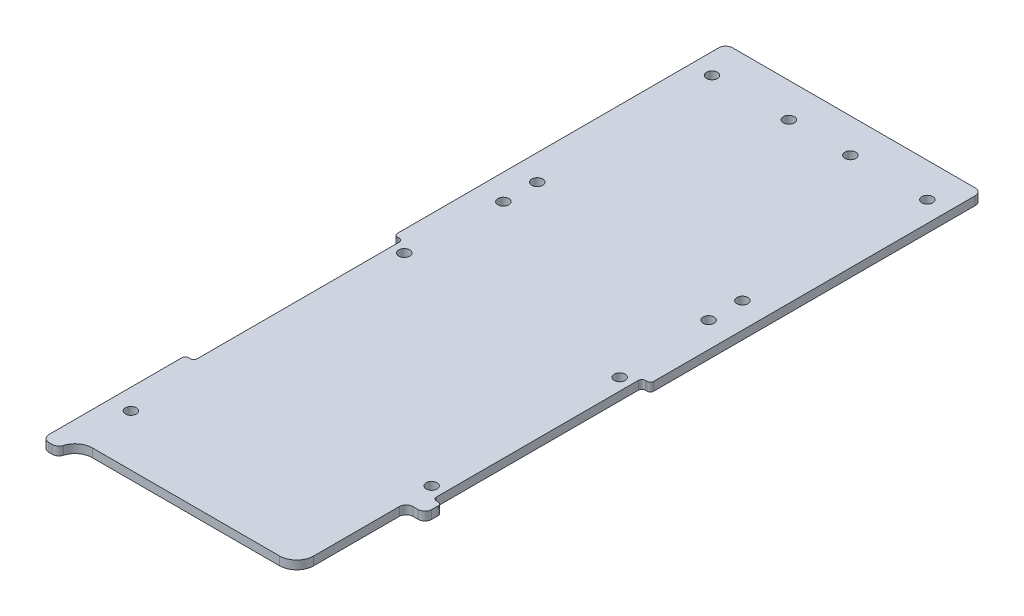
SolidWorks part; units mm, degrees
ref_plane "Front Plane" through (0, 0, 0) normal (0, 0, 1) x (1, 0, 0)
ref_plane "Top Plane" through (0, 0, 0) normal (0, 1, 0) x (1, 0, 0)
ref_plane "Right Plane" through (0, 0, 0) normal (1, 0, 0) x (0, 0, -1)
sketch "Sketch1" plane through (0, 0, 0) normal (0, 1, 0) x (1, 0, 0)
  line L0 (-39.9997, 0) -> (-39.9997, 114.3) construction
  line L1 (-47.625, 127) -> (47.625, 127)
  line L2 (-47.625, 127) -> (-47.625, -127)
  line L3 (-47.625, -127) -> (47.625, -127)
  line L4 (47.625, 127) -> (47.625, -127)
  line L5 (-47.625, 127) -> (47.625, -127) construction
  line L6 (-47.625, -127) -> (47.625, 127) construction
  line L7 (0, 0) -> (0, 127) construction
  line L8 (-39.9997, 0) -> (-39.9997, -101.6) construction
  line L9 (-39.9997, 0) -> (0, 0) construction
  line L10 (-41.275, -127) -> (-41.275, -120.65)
  line L11 (-41.275, -120.65) -> (41.275, -120.65)
  line L12 (41.275, -120.65) -> (41.275, -127)
  line L13 (-39.9997, 114.3) -> (-11.4247, 114.3) construction
  line L14 (39.9997, 114.3) -> (11.4247, 114.3) construction
  circle A0 centre (-39.9997, 114.3) radius 2.032
  circle A1 centre (-39.9997, 0) radius 2.032
  circle A2 centre (-39.9997, -101.6) radius 2.032
  circle A3 centre (39.9997, -101.6) radius 2.032
  circle A4 centre (39.9997, 0) radius 2.032
  circle A5 centre (39.9997, 114.3) radius 2.032
  circle A6 centre (-11.4247, 114.3) radius 2.032
  circle A7 centre (11.4247, 114.3) radius 2.032
  circle A8 centre (-39.9997, -69.85) radius 2.032
  circle A9 centre (39.9997, -69.85) radius 2.032
  point P0 (0, 0)
  dimension "D4" = 4.064
  dimension "D10" = 28.575
  dimension "D1" = 95.25
  dimension "D2" = 254
  dimension "D3" = 7.6253
  dimension "D5" = 12.7
  dimension "D6" = 25.4
  dimension "D7" = 6.35
  dimension "D8" = 6.35
  dimension "D9" = 6.35
  dimension "D11" = 69.85
extrude "Boss-Extrude1" add sketch "Sketch1" along normal blind 3.175 contours L4 L1 L2 L3 A4 A0 A1 A2 A3 A5 | A8 | A3 region at (0, 0, -2.6944) region at (39.9997, 0, 101.6) region at (-39.9997, 0, 69.85)
fillet "Fillet1" radius 2.54 4 edges at (-47.625, 1.5875, -127) (47.625, 1.5875, -127) (47.625, 1.5875, 127) (-47.625, 1.5875, 127)
fillet "Fillet2" radius 2.54 2 edges at (41.275, 1.5875, 127) (-41.275, 1.5875, 127)
fillet "Fillet3" radius 6.35 2 edges at (41.275, 1.5875, 120.65) (-41.275, 1.5875, 120.65)
sketch "Sketch2" plane through (0, 0, 0) normal (0, -1, 0) x (1, 0, 0)
  line L0 (41.9117, 131.8831) -> (41.9117, 109.8659) construction
  line L1 (41.9117, 109.8659) -> (41.9117, 106.3879) construction
  line L2 (41.9117, 83.271) -> (41.9117, 82.5325) construction
  line L3 (41.9117, 82.5325) -> (41.9117, 81.2514) construction
  line L4 (41.9117, 83.271) -> (41.9117, 106.3879) construction
  line L5 (41.9117, 131.8831) -> (41.9117, 109.8659)
  line L6 (41.9117, 109.8659) -> (41.9117, 106.3879)
  line L7 (41.9117, 83.271) -> (41.9117, 82.5325)
  line L8 (41.9117, 82.5325) -> (41.9117, 81.2514)
  line L9 (41.9117, 83.271) -> (41.9117, 106.3879)
  line L10 (41.9117, 81.2514) -> (47.625, 81.2514)
  line L11 (47.625, -124.46) -> (47.625, 124.46) construction
  line L12 (41.9117, 131.8831) -> (47.625, 131.8831)
  line L13 (47.625, 131.8831) -> (47.625, 81.2514)
  line L14 (40.6417, 79.9814) -> (48.895, 79.9814)
  line L15 (48.895, 133.1531) -> (48.895, 79.9814)
  line L16 (40.6417, 133.1531) -> (48.895, 133.1531)
  line L17 (40.6417, 133.1531) -> (40.6417, 109.8659)
  line L18 (40.6417, 109.8659) -> (40.6417, 106.3879)
  line L19 (40.6417, 83.271) -> (40.6417, 106.3879)
  line L20 (40.6417, 83.271) -> (40.6417, 82.5325)
  line L21 (40.6417, 82.5325) -> (40.6417, 79.9814)
  arc M7 (43.815, 127) -> (41.3809, 125.1857) centre (43.815, 124.46) ccw
  arc M8 (41.3809, 125.1857) -> (35.2956, 120.65) centre (35.2956, 127) cw
  line M18 (47.625, -124.46) -> (47.625, 124.46)
  dimension "D1" = 1.27
extrude "Cut-Extrude1" cut sketch "Sketch2" against normal through all contours L20 L21 L14 L10 L8 L7 L9 L19 M18 | L19 L9 L6 L5 L17 L18 M7 M8 | L13 L10 L8 L7 L9 L6 L5 L12 region at (41.6767, 0, 99.9811)
fillet "Fillet4" radius 6.35 1 edges at (40.6417, 1.5875, 123.5734)
fillet "Fillet5" radius 2.54 2 edges at (47.625, 1.5875, 79.9814) (40.6417, 1.5875, 79.9814)
sketch "Sketch3" plane through (0, 0, 0) normal (0, -1, 0) x (1, 0, 0)
  line L0 (-36.3088, -49.7791) -> (-39.9156, -49.7791) construction
  line L1 (-40.4236, -49.276) -> (-40.4236, -45.7043) construction
  line L2 (-35.8008, -45.7043) -> (-35.8008, -49.276) construction
  line L3 (-39.9156, -45.2013) -> (-36.3088, -45.2013) construction
  line L4 (-36.3088, -37.2027) -> (-39.9156, -37.2027) construction
  line L5 (-35.8008, -33.1279) -> (-35.8008, -36.6996) construction
  line L6 (-40.4236, -36.6996) -> (-40.4236, -33.1279) construction
  line L7 (-39.9156, -32.6249) -> (-36.3088, -32.6249) construction
  line L8 (36.2844, -32.6249) -> (39.8912, -32.6249) construction
  line L9 (40.3992, -33.1279) -> (40.3992, -36.6996) construction
  line L10 (39.8912, -37.2027) -> (36.2844, -37.2027) construction
  line L11 (35.7764, -36.6996) -> (35.7764, -33.1279) construction
  line L12 (36.2844, -45.2013) -> (39.8912, -45.2013) construction
  line L13 (35.7764, -49.276) -> (35.7764, -45.7043) construction
  line L14 (40.3992, -45.7043) -> (40.3992, -49.276) construction
  line L15 (39.8912, -49.7791) -> (36.2844, -49.7791) construction
  line L16 (-36.3088, -49.7791) -> (-39.9156, -49.7791)
  line L17 (-40.4236, -49.276) -> (-40.4236, -45.7043)
  line L18 (-35.8008, -45.7043) -> (-35.8008, -49.276)
  line L19 (-39.9156, -45.2013) -> (-36.3088, -45.2013)
  line L20 (-36.3088, -37.2027) -> (-39.9156, -37.2027)
  line L21 (-35.8008, -33.1279) -> (-35.8008, -36.6996)
  line L22 (-40.4236, -36.6996) -> (-40.4236, -33.1279)
  line L23 (-39.9156, -32.6249) -> (-36.3088, -32.6249)
  line L24 (36.2844, -32.6249) -> (39.8912, -32.6249)
  line L25 (40.3992, -33.1279) -> (40.3992, -36.6996)
  line L26 (39.8912, -37.2027) -> (36.2844, -37.2027)
  line L27 (35.7764, -36.6996) -> (35.7764, -33.1279)
  line L28 (36.2844, -45.2013) -> (39.8912, -45.2013)
  line L29 (35.7764, -49.276) -> (35.7764, -45.7043)
  line L30 (40.3992, -45.7043) -> (40.3992, -49.276)
  line L31 (39.8912, -49.7791) -> (36.2844, -49.7791)
  line L32 (-47.625, -25.836) -> (47.625, -25.836)
  line L33 (-47.625, -124.46) -> (-47.625, 124.46) construction
  line L34 (47.625, -124.46) -> (47.625, 77.4414) construction
  line L35 (0, -25.836) -> (0, -56.0686) construction
  line L38 (134.362, -51.414) -> (184.1378, -51.414)
  line L39 (184.1378, -51.414) -> (184.1378, -43.4909)
  line L40 (184.1378, -43.4909) -> (182.3344, -43.4909)
  line L41 (181.8264, -42.9878) -> (181.8264, -39.4161)
  line L42 (182.3344, -38.9131) -> (184.1378, -38.9131)
  line L43 (184.1378, -38.9131) -> (184.1378, -30.9899)
  line L44 (184.1378, -30.9899) -> (134.362, -30.9899)
  line L45 (134.362, -30.9899) -> (133.3378, -32.0042)
  line L46 (133.3378, -32.0042) -> (132.3136, -30.9899)
  line L47 (132.3136, -30.9899) -> (70.862, -30.9899)
  line L48 (70.862, -30.9899) -> (69.8378, -32.0042)
  line L49 (69.8378, -32.0042) -> (68.8136, -30.9899)
  line L50 (68.8136, -30.9899) -> (7.362, -30.9899)
  line L51 (7.362, -30.9899) -> (6.3378, -32.0042)
  line L52 (6.3378, -32.0042) -> (5.3136, -30.9899)
  line L53 (5.3136, -30.9899) -> (-56.138, -30.9899)
  line L54 (-56.138, -30.9899) -> (-57.1622, -32.0042)
  line L55 (-57.1622, -32.0042) -> (-58.1864, -30.9899)
  line L56 (-58.1864, -30.9899) -> (-119.638, -30.9899)
  line L57 (-119.638, -30.9899) -> (-120.6622, -32.0042)
  line L58 (-120.6622, -32.0042) -> (-121.6864, -30.9899)
  line L59 (-121.6864, -30.9899) -> (-184.1622, -30.9899)
  line L60 (-184.1622, -30.9899) -> (-184.1622, -51.414)
  line L61 (-184.1622, -51.414) -> (-121.6864, -51.414)
  line L62 (-121.6864, -51.414) -> (-120.6622, -50.3998)
  line L63 (-120.6622, -50.3998) -> (-119.638, -51.414)
  line L64 (-119.638, -51.414) -> (-58.1864, -51.414)
  line L65 (-58.1864, -51.414) -> (-57.1622, -50.3998)
  line L66 (-57.1622, -50.3998) -> (-56.138, -51.414)
  line L67 (-56.138, -51.414) -> (5.3136, -51.414)
  line L68 (5.3136, -51.414) -> (6.3378, -50.3998)
  line L69 (6.3378, -50.3998) -> (7.362, -51.414)
  line L70 (7.362, -51.414) -> (68.8136, -51.414)
  line L71 (68.8136, -51.414) -> (69.8378, -50.3998)
  line L72 (69.8378, -50.3998) -> (70.862, -51.414)
  line L73 (70.862, -51.414) -> (132.3136, -51.414)
  line L74 (132.3136, -51.414) -> (133.3378, -50.3998)
  line L75 (133.3378, -50.3998) -> (134.362, -51.414)
  line L76 (134.362, -51.414) -> (184.1378, -51.414)
  line L77 (184.1378, -51.414) -> (184.1378, -43.4909)
  line L78 (184.1378, -43.4909) -> (182.3344, -43.4909)
  line L79 (181.8264, -42.9878) -> (181.8264, -39.4161)
  line L80 (182.3344, -38.9131) -> (184.1378, -38.9131)
  line L81 (184.1378, -38.9131) -> (184.1378, -30.9899)
  line L82 (184.1378, -30.9899) -> (134.362, -30.9899)
  line L83 (134.362, -30.9899) -> (133.3378, -32.0042)
  line L84 (133.3378, -32.0042) -> (132.3136, -30.9899)
  line L85 (132.3136, -30.9899) -> (70.862, -30.9899)
  line L86 (70.862, -30.9899) -> (69.8378, -32.0042)
  line L87 (69.8378, -32.0042) -> (68.8136, -30.9899)
  line L88 (68.8136, -30.9899) -> (7.362, -30.9899)
  line L89 (7.362, -30.9899) -> (6.3378, -32.0042)
  line L90 (6.3378, -32.0042) -> (5.3136, -30.9899)
  line L91 (5.3136, -30.9899) -> (-56.138, -30.9899)
  line L92 (-56.138, -30.9899) -> (-57.1622, -32.0042)
  line L93 (-57.1622, -32.0042) -> (-58.1864, -30.9899)
  line L94 (-58.1864, -30.9899) -> (-119.638, -30.9899)
  line L95 (-119.638, -30.9899) -> (-120.6622, -32.0042)
  line L96 (-120.6622, -32.0042) -> (-121.6864, -30.9899)
  line L97 (-121.6864, -30.9899) -> (-184.1622, -30.9899)
  line L98 (-184.1622, -30.9899) -> (-184.1622, -51.414)
  line L99 (-184.1622, -51.414) -> (-121.6864, -51.414)
  line L100 (-121.6864, -51.414) -> (-120.6622, -50.3998)
  line L101 (-120.6622, -50.3998) -> (-119.638, -51.414)
  line L102 (-119.638, -51.414) -> (-58.1864, -51.414)
  line L103 (-58.1864, -51.414) -> (-57.1622, -50.3998)
  line L104 (-57.1622, -50.3998) -> (-56.138, -51.414)
  line L105 (-56.138, -51.414) -> (5.3136, -51.414)
  line L106 (5.3136, -51.414) -> (6.3378, -50.3998)
  line L107 (6.3378, -50.3998) -> (7.362, -51.414)
  line L108 (7.362, -51.414) -> (68.8136, -51.414)
  line L109 (68.8136, -51.414) -> (69.8378, -50.3998)
  line L110 (69.8378, -50.3998) -> (70.862, -51.414)
  line L111 (70.862, -51.414) -> (132.3136, -51.414)
  line L112 (132.3136, -51.414) -> (133.3378, -50.3998)
  line L113 (133.3378, -50.3998) -> (134.362, -51.414)
  line L1362 (-40.4236, -34.9138) -> (-35.8008, -34.9138)
  line L1857 (-38.1122, -32.6249) -> (-38.1122, -37.2027)
  line L1858 (-38.1122, -45.2013) -> (-38.1122, -49.7791)
  line L1859 (-40.4236, -47.4902) -> (-35.8008, -47.4902)
  circle A0 centre (-38.1122, -34.9138) radius 2.032
  circle A1 centre (-38.1122, -47.4902) radius 2.032
  circle A2 centre (38.1122, -47.4902) radius 2.032
  circle A3 centre (38.1122, -34.9138) radius 2.032
  ellipse E0 centre (-39.9156, -45.7043) end of major axis (-39.4076, -45.7043) minor radius 0.5031 (-39.9156, -45.2013) -> (-40.4236, -45.7043) ccw construction
  ellipse E1 centre (-39.9156, -49.276) end of major axis (-39.4076, -49.276) minor radius 0.5031 (-40.4236, -49.276) -> (-39.9156, -49.7791) ccw construction
  ellipse E2 centre (182.3344, -42.9878) end of major axis (182.8424, -42.9878) minor radius 0.5031 (181.8264, -42.9878) -> (182.3344, -43.4909) ccw
  ellipse E3 centre (182.3344, -39.4161) end of major axis (182.8424, -39.4161) minor radius 0.5031 (182.3344, -38.9131) -> (181.8264, -39.4161) ccw
  ellipse E4 centre (182.3344, -42.9878) end of major axis (182.8424, -42.9878) minor radius 0.5031 (181.8264, -42.9878) -> (182.3344, -43.4909) ccw
  ellipse E5 centre (182.3344, -39.4161) end of major axis (182.8424, -39.4161) minor radius 0.5031 (182.3344, -38.9131) -> (181.8264, -39.4161) ccw
  ellipse E6 centre (-36.3088, -49.276) end of major axis (-35.8008, -49.276) minor radius 0.5031 (-36.3088, -49.7791) -> (-35.8008, -49.276) ccw construction
  ellipse E7 centre (-36.3088, -45.7043) end of major axis (-35.8008, -45.7043) minor radius 0.5031 (-35.8008, -45.7043) -> (-36.3088, -45.2013) ccw construction
  ellipse E8 centre (-39.9156, -36.6996) end of major axis (-39.4076, -36.6996) minor radius 0.5031 (-40.4236, -36.6996) -> (-39.9156, -37.2027) ccw construction
  ellipse E9 centre (-36.3088, -36.6996) end of major axis (-35.8008, -36.6996) minor radius 0.5031 (-36.3088, -37.2027) -> (-35.8008, -36.6996) ccw construction
  ellipse E10 centre (-36.3088, -33.1279) end of major axis (-35.8008, -33.1279) minor radius 0.5031 (-35.8008, -33.1279) -> (-36.3088, -32.6249) ccw construction
  ellipse E11 centre (-39.9156, -33.1279) end of major axis (-39.4076, -33.1279) minor radius 0.5031 (-39.9156, -32.6249) -> (-40.4236, -33.1279) ccw construction
  ellipse E12 centre (39.8912, -33.1279) end of major axis (40.3992, -33.1279) minor radius 0.5031 (40.3992, -33.1279) -> (39.8912, -32.6249) ccw construction
  ellipse E13 centre (36.2844, -33.1279) end of major axis (36.7924, -33.1279) minor radius 0.5031 (36.2844, -32.6249) -> (35.7764, -33.1279) ccw construction
  ellipse E14 centre (39.8912, -36.6996) end of major axis (40.3992, -36.6996) minor radius 0.5031 (39.8912, -37.2027) -> (40.3992, -36.6996) ccw construction
  ellipse E15 centre (36.2844, -36.6996) end of major axis (36.7924, -36.6996) minor radius 0.5031 (35.7764, -36.6996) -> (36.2844, -37.2027) ccw construction
  ellipse E16 centre (36.2844, -45.7043) end of major axis (36.7924, -45.7043) minor radius 0.5031 (36.2844, -45.2013) -> (35.7764, -45.7043) ccw construction
  ellipse E17 centre (36.2844, -49.276) end of major axis (36.7924, -49.276) minor radius 0.5031 (35.7764, -49.276) -> (36.2844, -49.7791) ccw construction
  ellipse E18 centre (39.8912, -45.7043) end of major axis (40.3992, -45.7043) minor radius 0.5031 (40.3992, -45.7043) -> (39.8912, -45.2013) ccw construction
  ellipse E19 centre (39.8912, -49.276) end of major axis (40.3992, -49.276) minor radius 0.5031 (39.8912, -49.7791) -> (40.3992, -49.276) ccw construction
  ellipse E20 centre (-39.9156, -45.7043) end of major axis (-39.4076, -45.7043) minor radius 0.5031 (-39.9156, -45.2013) -> (-40.4236, -45.7043) ccw
  ellipse E21 centre (-39.9156, -49.276) end of major axis (-39.4076, -49.276) minor radius 0.5031 (-40.4236, -49.276) -> (-39.9156, -49.7791) ccw
  ellipse E22 centre (-36.3088, -49.276) end of major axis (-35.8008, -49.276) minor radius 0.5031 (-36.3088, -49.7791) -> (-35.8008, -49.276) ccw
  ellipse E23 centre (-36.3088, -45.7043) end of major axis (-35.8008, -45.7043) minor radius 0.5031 (-35.8008, -45.7043) -> (-36.3088, -45.2013) ccw
  ellipse E24 centre (-39.9156, -36.6996) end of major axis (-39.4076, -36.6996) minor radius 0.5031 (-40.4236, -36.6996) -> (-39.9156, -37.2027) ccw
  ellipse E25 centre (-36.3088, -36.6996) end of major axis (-35.8008, -36.6996) minor radius 0.5031 (-36.3088, -37.2027) -> (-35.8008, -36.6996) ccw
  ellipse E26 centre (-36.3088, -33.1279) end of major axis (-35.8008, -33.1279) minor radius 0.5031 (-35.8008, -33.1279) -> (-36.3088, -32.6249) ccw
  ellipse E27 centre (-39.9156, -33.1279) end of major axis (-39.4076, -33.1279) minor radius 0.5031 (-39.9156, -32.6249) -> (-40.4236, -33.1279) ccw
  ellipse E28 centre (39.8912, -33.1279) end of major axis (40.3992, -33.1279) minor radius 0.5031 (40.3992, -33.1279) -> (39.8912, -32.6249) ccw
  ellipse E29 centre (36.2844, -33.1279) end of major axis (36.7924, -33.1279) minor radius 0.5031 (36.2844, -32.6249) -> (35.7764, -33.1279) ccw
  ellipse E30 centre (39.8912, -36.6996) end of major axis (40.3992, -36.6996) minor radius 0.5031 (39.8912, -37.2027) -> (40.3992, -36.6996) ccw
  ellipse E31 centre (36.2844, -36.6996) end of major axis (36.7924, -36.6996) minor radius 0.5031 (35.7764, -36.6996) -> (36.2844, -37.2027) ccw
  ellipse E32 centre (36.2844, -45.7043) end of major axis (36.7924, -45.7043) minor radius 0.5031 (36.2844, -45.2013) -> (35.7764, -45.7043) ccw
  ellipse E33 centre (36.2844, -49.276) end of major axis (36.7924, -49.276) minor radius 0.5031 (35.7764, -49.276) -> (36.2844, -49.7791) ccw
  ellipse E34 centre (39.8912, -45.7043) end of major axis (40.3992, -45.7043) minor radius 0.5031 (40.3992, -45.7043) -> (39.8912, -45.2013) ccw
  ellipse E35 centre (39.8912, -49.276) end of major axis (40.3992, -49.276) minor radius 0.5031 (39.8912, -49.7791) -> (40.3992, -49.276) ccw
  dimension "D2" = 4.064
  dimension "D1" = 0
extrude "Cut-Extrude2" cut sketch "Sketch3" against normal through all contours A0 | A1 | A2 | A3
sketch "Sketch4" plane through (0, 3.175, 0) normal (0, 1, 0) x (1, 0, 0)
  line L0 (-44.45, 3.81) -> (-46.99, 3.81) construction
  line L1 (-46.99, 3.81) -> (-46.99, 121.92) construction
  line L2 (-42.545, 126.365) -> (-0.635, 126.365) construction
  line L3 (-0.635, 126.365) -> (-0.635, 107.95) construction
  line L4 (-6.35, 102.235) -> (-15.875, 102.235) construction
  line L5 (-22.86, 95.25) -> (-22.86, -115.57) construction
  line L6 (-27.305, -120.015) -> (-35.4551, -120.015) construction
  line L7 (-43.815, -126.365) -> (-45.085, -126.365) construction
  line L8 (-46.99, -124.46) -> (-46.99, -73.7819) construction
  line L9 (-46.99, -73.7819) -> (-44.45, -73.7819) construction
  line L10 (-44.45, -73.7819) -> (-44.45, 3.81) construction
  line L11 (-46.99, 3.81) -> (-44.45, 3.81)
  line L12 (-46.99, 121.92) -> (-46.99, 3.81)
  line L13 (-0.635, 126.365) -> (-42.545, 126.365)
  line L14 (-0.635, 107.95) -> (-0.635, 126.365)
  line L15 (-15.875, 102.235) -> (-6.35, 102.235)
  line L16 (-22.86, -115.57) -> (-22.86, 95.25)
  line L17 (-35.4551, -120.015) -> (-27.305, -120.015)
  line L18 (-45.085, -126.365) -> (-43.815, -126.365)
  line L19 (-46.99, -73.7819) -> (-46.99, -124.46)
  line L20 (-44.45, -73.7819) -> (-46.99, -73.7819)
  line L21 (-44.45, 3.81) -> (-44.45, -73.7819)
  line L22 (-46.99, 3.81) -> (-44.45, 3.81)
  line L23 (-46.99, 121.92) -> (-46.99, 3.81)
  line L24 (-0.635, 126.365) -> (-42.545, 126.365)
  line L25 (-0.635, 107.95) -> (-0.635, 126.365)
  line L26 (-15.875, 102.235) -> (-6.35, 102.235)
  line L27 (-22.86, -115.57) -> (-22.86, 95.25)
  line L28 (-35.4551, -120.015) -> (-27.305, -120.015)
  line L29 (-45.085, -126.365) -> (-43.815, -126.365)
  line L30 (-46.99, -73.7819) -> (-46.99, -124.46)
  line L31 (-44.45, -73.7819) -> (-46.99, -73.7819)
  line L32 (-44.45, 3.81) -> (-44.45, -73.7819)
  line L33 (40.64, -77.5286) -> (40.64, -117.0408) construction
  line L34 (35.4551, -120.015) -> (27.305, -120.015) construction
  line L35 (22.86, -115.57) -> (22.86, 95.25) construction
  line L36 (15.875, 102.235) -> (6.35, 102.235) construction
  line L37 (0.635, 107.95) -> (0.635, 126.365) construction
  line L38 (0.635, 126.365) -> (42.545, 126.365) construction
  line L39 (46.99, 121.92) -> (46.99, 3.81) construction
  line L40 (46.99, 3.81) -> (44.45, 3.81) construction
  line L41 (44.45, 3.81) -> (44.45, -73.7819) construction
  line L42 (44.45, -73.7819) -> (46.99, -73.7819) construction
  line L43 (46.99, -73.7819) -> (46.99, -77.5286) construction
  line L44 (46.99, -77.5286) -> (40.64, -77.5286) construction
  line L45 (-44.45, 3.81) -> (-46.99, 3.81)
  line L46 (-46.99, 3.81) -> (-46.99, 121.92)
  line L47 (-42.545, 126.365) -> (-0.635, 126.365)
  line L48 (-0.635, 126.365) -> (-0.635, 107.95)
  line L49 (-6.35, 102.235) -> (-15.875, 102.235)
  line L50 (-22.86, 95.25) -> (-22.86, -115.57)
  line L51 (-27.305, -120.015) -> (-35.4551, -120.015)
  line L52 (-43.815, -126.365) -> (-45.085, -126.365)
  line L53 (-46.99, -124.46) -> (-46.99, -73.7819)
  line L54 (-46.99, -73.7819) -> (-44.45, -73.7819)
  line L55 (-44.45, -73.7819) -> (-44.45, 3.81)
  line L56 (40.64, -77.5286) -> (40.64, -117.0408)
  line L57 (35.4551, -120.015) -> (27.305, -120.015)
  line L58 (22.86, -115.57) -> (22.86, 95.25)
  line L59 (15.875, 102.235) -> (6.35, 102.235)
  line L60 (0.635, 107.95) -> (0.635, 126.365)
  line L61 (0.635, 126.365) -> (42.545, 126.365)
  line L62 (46.99, 121.92) -> (46.99, 3.81)
  line L63 (46.99, 3.81) -> (44.45, 3.81)
  line L64 (44.45, 3.81) -> (44.45, -73.7819)
  line L65 (44.45, -73.7819) -> (46.99, -73.7819)
  line L66 (46.99, -73.7819) -> (46.99, -77.5286)
  line L67 (46.99, -77.5286) -> (40.64, -77.5286)
  line L178 (-46.99, 3.81) -> (-47.625, 3.81)
  line L179 (-47.625, 124.46) -> (-47.625, -124.46) construction
  line L180 (-46.99, -73.7819) -> (-47.625, -73.7819)
  line L181 (46.99, -73.7819) -> (47.625, -73.7819)
  line L182 (47.625, 124.46) -> (47.625, -77.4414) construction
  line L183 (46.99, 3.81) -> (47.625, 3.81)
  arc A0 (-42.545, 126.365) -> (-46.99, 121.92) centre (-42.545, 121.92) ccw construction
  arc A1 (-6.35, 102.235) -> (-0.635, 107.95) centre (-6.35, 107.95) ccw construction
  arc A2 (-15.875, 102.235) -> (-22.86, 95.25) centre (-15.875, 95.25) ccw construction
  arc A3 (-27.305, -120.015) -> (-22.86, -115.57) centre (-27.305, -115.57) ccw construction
  arc A4 (-35.4551, -120.015) -> (-41.9138, -124.3399) centre (-35.4551, -127) ccw construction
  arc A5 (-43.815, -126.365) -> (-41.9138, -124.3399) centre (-43.815, -124.46) ccw construction
  arc A6 (-46.99, -124.46) -> (-45.085, -126.365) centre (-45.085, -124.46) ccw construction
  arc A7 (-42.545, 126.365) -> (-46.99, 121.92) centre (-42.545, 121.92) ccw
  arc A8 (-6.35, 102.235) -> (-0.635, 107.95) centre (-6.35, 107.95) ccw
  arc A9 (-15.875, 102.235) -> (-22.86, 95.25) centre (-15.875, 95.25) ccw
  arc A10 (-27.305, -120.015) -> (-22.86, -115.57) centre (-27.305, -115.57) ccw
  arc A11 (-35.4551, -120.015) -> (-41.9138, -124.3399) centre (-35.4551, -127) ccw
  arc A12 (-43.815, -126.365) -> (-41.9138, -124.3399) centre (-43.815, -124.46) ccw
  arc A13 (-46.99, -124.46) -> (-45.085, -126.365) centre (-45.085, -124.46) ccw
  arc A14 (-42.545, 126.365) -> (-46.99, 121.92) centre (-42.545, 121.92) ccw
  arc A15 (-6.35, 102.235) -> (-0.635, 107.95) centre (-6.35, 107.95) ccw
  arc A16 (-15.875, 102.235) -> (-22.86, 95.25) centre (-15.875, 95.25) ccw
  arc A17 (-27.305, -120.015) -> (-22.86, -115.57) centre (-27.305, -115.57) ccw
  arc A18 (-35.4551, -120.015) -> (-41.9138, -124.3399) centre (-35.4551, -127) ccw
  arc A19 (-43.815, -126.365) -> (-41.9138, -124.3399) centre (-43.815, -124.46) ccw
  arc A20 (-46.99, -124.46) -> (-45.085, -126.365) centre (-45.085, -124.46) ccw
  arc A21 (36.8369, -120.153) -> (40.64, -117.0408) centre (37.465, -117.0408) ccw construction
  arc A22 (36.8369, -120.153) -> (35.4551, -120.015) centre (35.4551, -127) ccw construction
  arc A23 (22.86, -115.57) -> (27.305, -120.015) centre (27.305, -115.57) ccw construction
  arc A24 (22.86, 95.25) -> (15.875, 102.235) centre (15.875, 95.25) ccw construction
  arc A25 (0.635, 107.95) -> (6.35, 102.235) centre (6.35, 107.95) ccw construction
  arc A26 (46.99, 121.92) -> (42.545, 126.365) centre (42.545, 121.92) ccw construction
  arc A27 (-42.545, 126.365) -> (-46.99, 121.92) centre (-42.545, 121.92) ccw
  arc A28 (-6.35, 102.235) -> (-0.635, 107.95) centre (-6.35, 107.95) ccw
  arc A29 (-15.875, 102.235) -> (-22.86, 95.25) centre (-15.875, 95.25) ccw
  arc A30 (-27.305, -120.015) -> (-22.86, -115.57) centre (-27.305, -115.57) ccw
  arc A31 (-35.4551, -120.015) -> (-41.9138, -124.3399) centre (-35.4551, -127) ccw
  arc A32 (-43.815, -126.365) -> (-41.9138, -124.3399) centre (-43.815, -124.46) ccw
  arc A33 (-46.99, -124.46) -> (-45.085, -126.365) centre (-45.085, -124.46) ccw
  arc A34 (36.8369, -120.153) -> (40.64, -117.0408) centre (37.465, -117.0408) ccw
  arc A35 (36.8369, -120.153) -> (35.4551, -120.015) centre (35.4551, -127) ccw
  arc A36 (22.86, -115.57) -> (27.305, -120.015) centre (27.305, -115.57) ccw
  arc A37 (22.86, 95.25) -> (15.875, 102.235) centre (15.875, 95.25) ccw
  arc A38 (0.635, 107.95) -> (6.35, 102.235) centre (6.35, 107.95) ccw
  arc A39 (46.99, 121.92) -> (42.545, 126.365) centre (42.545, 121.92) ccw
  line M32 (47.625, -77.4414) -> (47.625, 124.46)
  line M36 (-47.625, 124.46) -> (-47.625, -124.46)
  dimension "D1" = 0
extrude "Cut-Extrude3" cut sketch "Sketch4" against normal through all and the other way through all contours L180 L31 L32 L22 L178 M36 | L183 L63 L64 L65 L181 M32 region at (-46.0375, 3.175, 34.986) region at (46.0375, 3.175, 34.986)
fillet "Fillet6" radius 1.27 8 edges at (-44.45, 1.5875, -3.81) (-44.45, 1.5875, 73.7819) (44.45, 1.5875, -3.81) (44.45, 1.5875, 73.7819) (47.625, 1.5875, 73.7819) (47.625, 1.5875, -3.81) (-47.625, 1.5875, 73.7819) (-47.625, 1.5875, -3.81)
